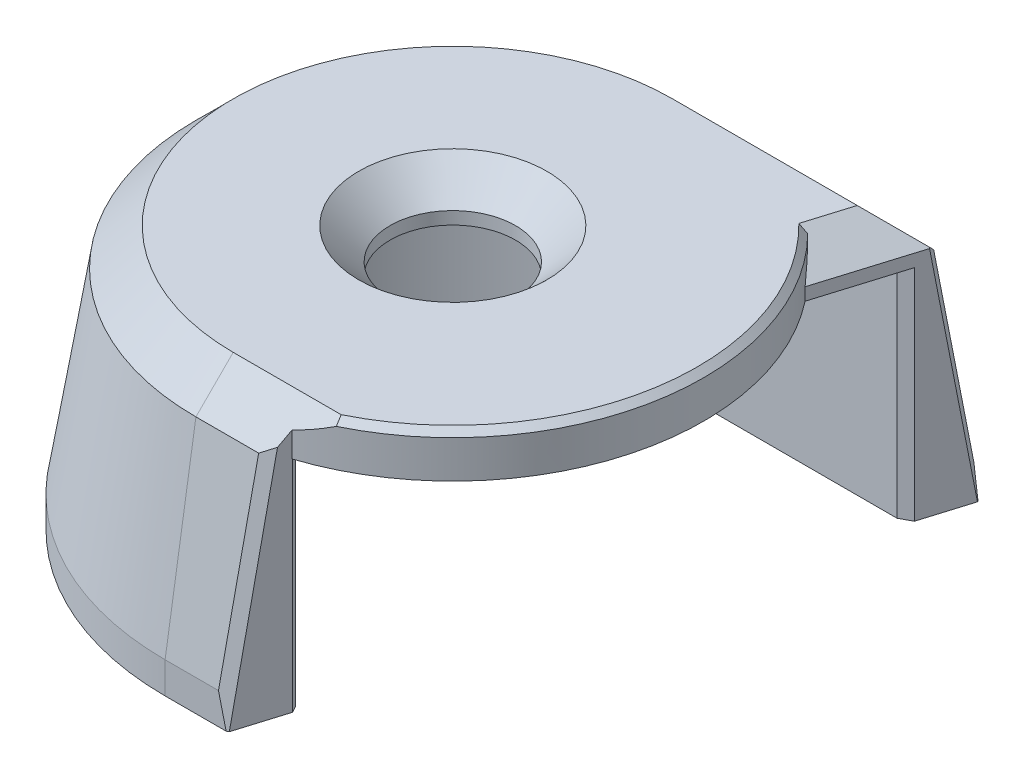
SolidWorks part; units mm, degrees
ref_plane "Front Plane" through (0, 0, 0) normal (0, 0, 1) x (1, 0, 0)
ref_plane "Top Plane" through (0, 0, 0) normal (0, 1, 0) x (1, 0, 0)
ref_plane "Right Plane" through (0, 0, 0) normal (1, 0, 0) x (0, 0, -1)
sketch "Sketch2" plane through (0, 0, 0) normal (1, 0, 0) x (0, 0, -1)
  line L0 (0, 0) -> (0, 39821.435) construction
  line L1 (37, 0) -> (45.85, 0)
  line L2 (45.85, 0) -> (45.85, 5)
  line L3 (45.85, 5) -> (40, 42)
  line L4 (40, 42) -> (0, 42)
  line L5 (0, 42) -> (0, 35)
  line L6 (0, 35) -> (37, 35)
  line L7 (37, 35) -> (37, 0)
  dimension "D1" = 91.7
  dimension "D2" = 35
  dimension "D3" = 7
  dimension "D4" = 74
  dimension "D5" = 3
  dimension "D6" = 5
revolve "Revolve1" add sketch "Sketch2" angle 180 about L0
sketch "Sketch7" plane through (0, 0, 0) normal (1, 0, 0) x (0, 0, -1)
  line L10 (-37, 0) -> (-37, 35)
  line L11 (-37, 35) -> (37, 35)
  line L12 (37, 35) -> (37, 0)
  line L13 (37, 0) -> (45.85, 0)
  line L14 (45.85, 0) -> (45.85, 5)
  line L15 (45.85, 5) -> (40, 42)
  line L16 (40, 42) -> (-40, 42)
  line L17 (-40, 42) -> (-45.85, 5)
  line L18 (-45.85, 5) -> (-45.85, 0)
  line L19 (-45.85, 0) -> (-37, 0)
  line L20 (-37, 0) -> (-37, 35)
  line L21 (-37, 35) -> (37, 35)
  line L22 (37, 35) -> (37, 0)
  line L23 (37, 0) -> (45.85, 0)
  line L24 (45.85, 0) -> (45.85, 5)
  line L25 (45.85, 5) -> (40, 42)
  line L26 (40, 42) -> (-40, 42)
  line L27 (-40, 42) -> (-45.85, 5)
  line L28 (-45.85, 5) -> (-45.85, 0)
  line L29 (-45.85, 0) -> (-37, 0)
  dimension "D1" = 0
extrude "Boss-Extrude1" add sketch "Sketch7" along normal blind 60
sketch "Sketch8" plane through (0, 0, 0) normal (0, 1, 0) x (1, 0, 0)
  line L0 (10, -45.85) -> (38, 45.85)
  line L1 (60, -45.85) -> (0, -45.85) construction
  line L2 (60, 45.85) -> (0, 45.85) construction
  line L3 (0, 0) -> (0, 26.5046) construction
  line L4 (38, 45.85) -> (138, 45.85)
  line L5 (138, 45.85) -> (138, -45.85)
  line L6 (138, -45.85) -> (10, -45.85)
  arc A0 (0, 45.85) -> (0, -45.85) centre (0, 0) ccw construction
  arc A1 (0, 45.85) -> (0, -45.85) centre (0, 0) ccw construction
  circle A2 centre (0, 0) radius 10
  dimension "D4" = 20
  dimension "D1" = 38
  dimension "D2" = 10
  dimension "D3" = 100
extrude "Cut-Extrude2" cut sketch "Sketch8" against normal through all both and the other way through all
sketch "Sketch9" plane through (0, 42, 0) normal (0, 1, 0) x (1, 0, 0)
  line L0 (36.2137, 40) -> (11.7863, -40) construction
  line L1 (31.5198, 24.6273) -> (0, -40)
  arc A0 (0, -40) -> (31.5198, 24.6273) centre (0, 0) ccw
extrude "Boss-Extrude2" add sketch "Sketch9" against normal up to surface (7 mm away) up to face at (0, 35, -10)
chamfer "Chamfer1" distance 5 angle 45 6 edges at (5.8931, 42, 40) (18.1069, 42, -40) (-40, 42, 0) (12.0864, 42, 39.0169) (33.8668, 42, -32.3136) (0, 42, 10) first distance on face at (11.3683, 42, 3.0641)
chamfer "Chamfer2" distance 1 angle 45 5 edges at (39.6716, 42, 5.1152) (12.7023, 17.5, 37) (35.2977, 17.5, -37) (37.2502, 20.5305, -43.3945) (10.7498, 20.5305, 43.3945) first distance on face at (27.9043, 38.2909, 6.6716) first distance on face at (11.6682, 21.4325, 40.3867) first distance on face at (35.2936, 23.1326, -36.9867)
